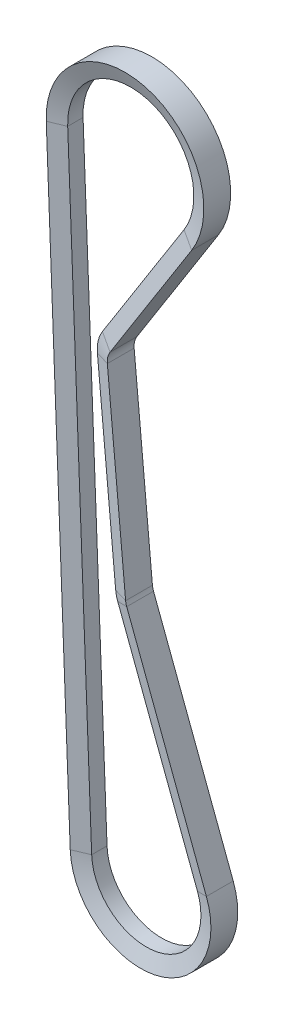
SolidWorks part; units mm, degrees
ref_plane "Front Plane" through (0, 0, 0) normal (0, 0, 1) x (1, 0, 0)
ref_plane "Top Plane" through (0, 0, 0) normal (0, 1, 0) x (1, 0, 0)
ref_plane "Right Plane" through (0, 0, 0) normal (1, 0, 0) x (0, 0, -1)
sketch "Sketch2" plane through (0, 0, 0) normal (0, 0, 1) x (1, 0, 0)
  line L0 (0, 0) -> (1, 0) construction
  line L1 (0, 0) -> (0, 1) construction
  line L12 (-24.9813, -0.9678) -> (-33.4972, 218.8468)
  line L14 (18.1433, 204.9598) -> (-10.8439, 159.1458)
  line L15 (-11.8003, 155.1613) -> (-5.3041, 85.4634)
  line L16 (-4.9222, 83.8096) -> (23.3883, 8.831)
  arc A4 (-33.4972, 218.8468) -> (18.1433, 204.9598) centre (-5.5182, 219.9308) cw
  arc A7 (23.3883, 8.831) -> (-24.9813, -0.9678) centre (0, 0) cw
  arc A8 (-10.8439, 159.1458) -> (-11.8003, 155.1613) centre (-5.4778, 155.7506) ccw
  arc A9 (-5.3041, 85.4634) -> (-4.9222, 83.8096) centre (1.0185, 86.0527) ccw
ref_plane "Plane4" through (23.3883, 8.831, 0) normal (0.3532, -0.9355, 0) x (-0.9355, -0.3532, 0)
sketch "Sketch3" plane through (23.3883, 8.831, 0) normal (0.3532, -0.9355, 0) x (-0.9355, -0.3532, 0)
  line L0 (0, -4.7625) -> (0, 4.7625)
  line L1 (0, -4.7625) -> (5.588, -2.7286)
  line L2 (5.588, -2.7286) -> (5.588, 2.7286)
  line L3 (5.588, 2.7286) -> (0, 4.7625)
  line L4 (0, 0) -> (5.588, 0) construction
  dimension "D1" = 9.525
  dimension "D2" = 5.588
  dimension "D3" = 40
sweep "Sweep1" add profiles "Sketch3" path "Sketch2"
